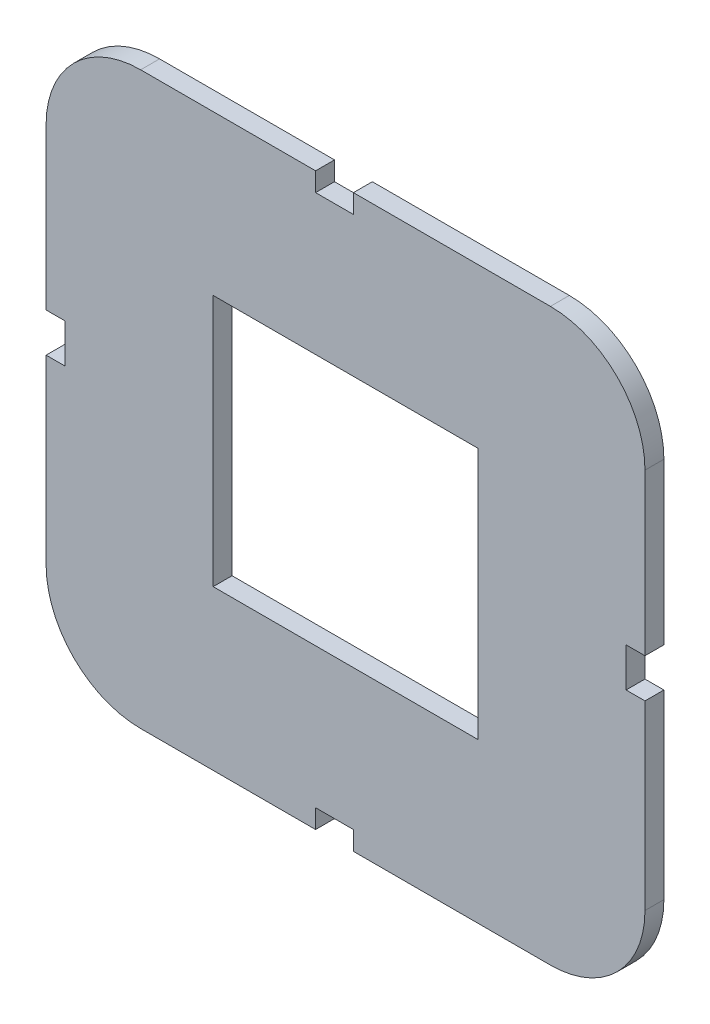
SolidWorks part; units mm, degrees
ref_plane "Front Plane" through (0, 0, 0) normal (0, 0, 1) x (1, 0, 0)
ref_plane "Top Plane" through (0, 0, 0) normal (0, 1, 0) x (1, 0, 0)
ref_plane "Right Plane" through (0, 0, 0) normal (1, 0, 0) x (0, 0, -1)
sketch "Sketch1" plane through (0, 0, 0) normal (0, 0, 1) x (1, 0, 0)
  line L0 (-47.5, -1.45) -> (-44.5, -1.45)
  line L1 (-32.5, -45.25) -> (-4.75, -45.25)
  line L2 (-47.5, -30.25) -> (-47.5, -1.45)
  line L3 (-32.5, 45.25) -> (-4.75, 45.25)
  line L4 (47.5, -30.25) -> (47.5, -1.45)
  line L5 (-47.5, -45.25) -> (47.5, 45.25) construction
  line L6 (-47.5, 45.25) -> (47.5, -45.25) construction
  line L7 (-44.5, -1.45) -> (-44.5, 4.75)
  line L8 (-44.5, 4.75) -> (-47.5, 4.75)
  line L9 (47.5, -1.45) -> (44.5, -1.45)
  line L10 (44.5, -1.45) -> (44.5, 4.75)
  line L11 (44.5, 4.75) -> (47.5, 4.75)
  line L12 (-1.75, 45.25) -> (-1.75, -45.25) construction
  line L13 (-44.5, 1.65) -> (44.5, 1.65) construction
  line L14 (-4.75, -45.25) -> (-4.75, -42.25)
  line L15 (-4.75, -42.25) -> (1.25, -42.25)
  line L16 (1.25, -42.25) -> (1.25, -45.25)
  line L17 (-4.75, 45.25) -> (-4.75, 42.25)
  line L18 (-4.75, 42.25) -> (1.25, 42.25)
  line L19 (1.25, 42.25) -> (1.25, 45.25)
  line L20 (-47.5, 4.75) -> (-47.5, 30.25)
  line L21 (1.25, 45.25) -> (32.5, 45.25)
  line L22 (47.5, 4.75) -> (47.5, 30.25)
  line L23 (1.25, -45.25) -> (32.5, -45.25)
  line L25 (21, 20.0053) -> (-21, 20.0053)
  line L26 (21, 20.0053) -> (21, -20.0053)
  line L27 (21, -20.0053) -> (-21, -20.0053)
  line L28 (-21, 20.0053) -> (-21, -20.0053)
  line L29 (21, 20.0053) -> (-21, -20.0053) construction
  line L30 (21, -20.0053) -> (-21, 20.0053) construction
  arc A0 (32.5, 45.25) -> (47.5, 30.25) centre (32.5, 30.25) cw
  arc A1 (32.5, -45.25) -> (47.5, -30.25) centre (32.5, -30.25) ccw
  arc A2 (-32.5, -45.25) -> (-47.5, -30.25) centre (-32.5, -30.25) cw
  arc A3 (-47.5, 30.25) -> (-32.5, 45.25) centre (-32.5, 30.25) cw
  point P0 (0, 0)
  point P27 (0, 0)
  dimension "D12" = 15
  dimension "D1" = 95
  dimension "D2" = 90.5
  dimension "D3" = 6.2
  dimension "D4" = 3
  dimension "D5" = 3
  dimension "D6" = 43.8
  dimension "D7" = 3
  dimension "D8" = 6
  dimension "D9" = 6
  dimension "D10" = 3
  dimension "D11" = 42
extrude "Boss-Extrude1" add sketch "Sketch1" along normal blind 3
